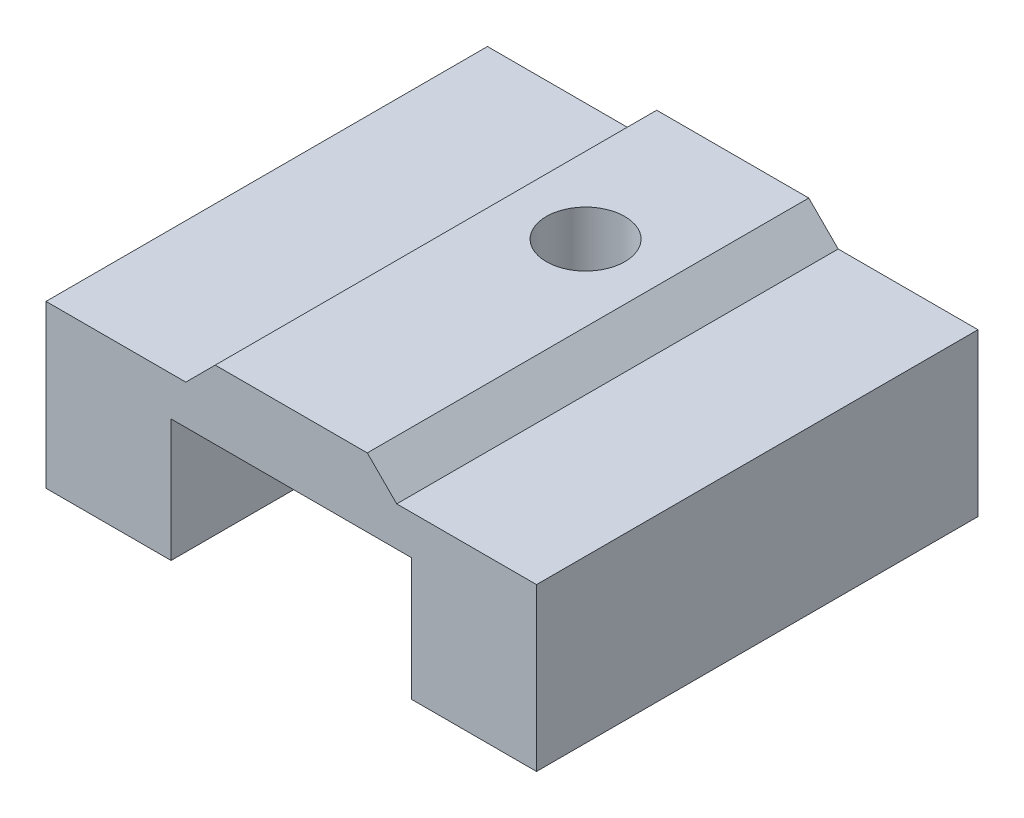
SolidWorks part; units mm, degrees
ref_plane "Front" through (0, 0, 0) normal (0, 0, 1) x (1, 0, 0)
ref_plane "Top" through (0, 0, 0) normal (0, 1, 0) x (1, 0, 0)
ref_plane "Right" through (0, 0, 0) normal (1, 0, 0) x (0, 0, -1)
sketch "Sketch2" plane through (0, 0, 0) normal (0, 0, 1) x (1, 0, 0)
  line L0 (-3.1, 0) -> (3.1, 0)
  line L1 (3.1, 0) -> (3.1, -1.2)
  line L2 (3.1, -1.2) -> (10, -1.2)
  line L3 (10, -1.2) -> (10, -7.8)
  line L4 (10, -7.8) -> (4.9, -7.8)
  line L5 (4.9, -7.8) -> (4.9, -2.8)
  line L6 (4.9, -2.8) -> (-4.9, -2.8)
  line L7 (-4.9, -2.8) -> (-4.9, -7.8)
  line L8 (-4.9, -7.8) -> (-10, -7.8)
  line L9 (-10, -7.8) -> (-10, -1.2)
  line L10 (-10, -1.2) -> (-3.1, -1.2)
  line L11 (-3.1, -1.2) -> (-3.1, 0)
  point P12 (-3.0711, -3.6)
  dimension "D1" = 6.2
  dimension "D2" = 9.8
  dimension "D3" = 20
  dimension "D4" = 1.6
  dimension "D5" = 1.2
  dimension "D6" = 5
extrude "Boss-Extrude2" add sketch "Sketch2" along normal blind 18
sketch "Sketch3" plane through (0, 0, 0) normal (0, 1, 0) x (1, 0, 0)
  line L0 (3.1, 0) -> (-3.1, 0) construction
  circle A0 centre (0, -6) radius 1.6
  point P4 (0, 0)
  dimension "D1" = 3.2
  dimension "D2" = 6
extrude "Cut-Extrude1" cut sketch "Sketch3" against normal blind 24
chamfer "Chamfer1" distance 1.2 angle 45 2 edges at (3.1, -1.2, 9) (-3.1, -1.2, 9)
